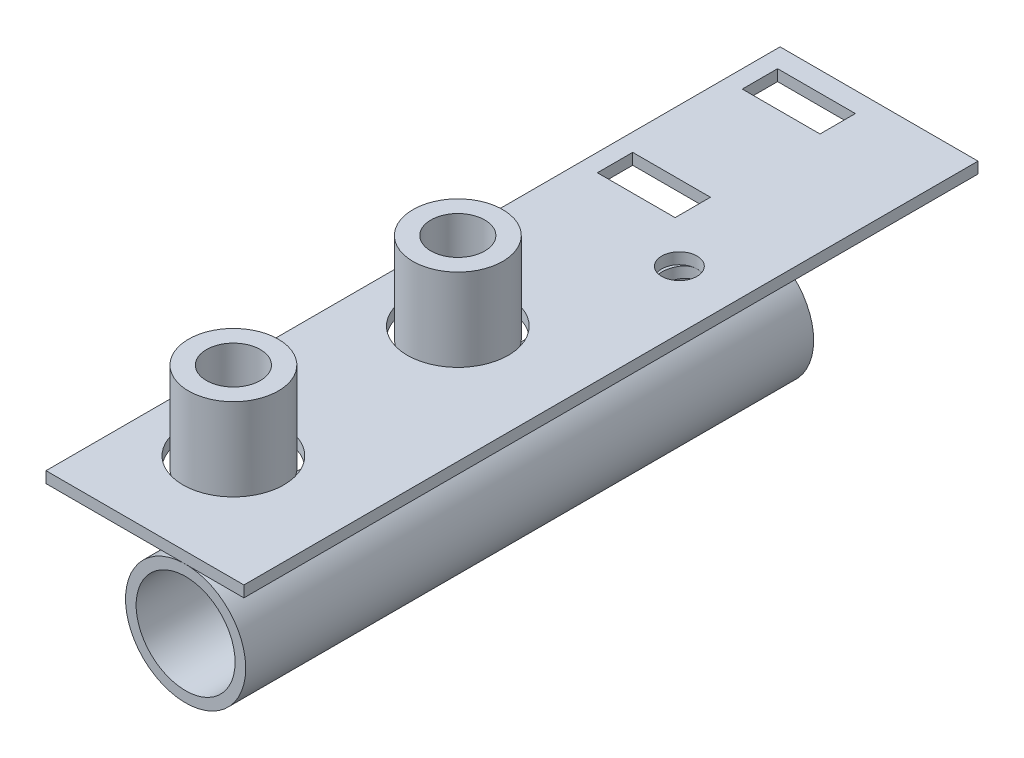
SolidWorks part; units mm, degrees
note: The reader was unsure of these and kept them because the rebuilt part matched: shared geometry of "Sketch6<4>".
other "DetailItem3"
other "Weld Folder"
ref_plane "Front Plane" through (0, 0, 0) normal (0, 0, 1) x (1, 0, 0)
ref_plane "Top Plane" through (0, 0, 0) normal (0, 1, 0) x (1, 0, 0)
ref_plane "Right Plane" through (0, 0, 0) normal (1, 0, 0) x (0, 0, -1)
sketch "Sketch1" plane through (0, 0, 0) normal (0, 1, 0) x (1, 0, 0)
  line L0 (-63.4061, 36.8) -> (49936.5939, 36.8) construction
  line L1 (16.5, -139.7) -> (-39.5, -139.7)
  line L2 (16.5, -139.7) -> (16.5, 68)
  line L3 (16.5, 68) -> (-39.5, 68)
  line L4 (-39.5, -139.7) -> (-39.5, 68)
  line L5 (16.5, -139.7) -> (-39.5, 68) construction
  line L6 (16.5, 68) -> (-39.5, -139.7) construction
  line L7 (-34.5, 62.3) -> (-12.5, 62.3)
  line L8 (-34.5, 62.3) -> (-34.5, 52.3)
  line L9 (-34.5, 52.3) -> (-12.5, 52.3)
  line L10 (-12.5, 62.3) -> (-12.5, 52.3)
  line L11 (-34.5, 62.3) -> (-12.5, 52.3) construction
  line L12 (-34.5, 52.3) -> (-12.5, 62.3) construction
  line L13 (-12.5, 11.3) -> (-12.5, 21.3)
  line L14 (-34.5, 11.3) -> (-12.5, 11.3)
  line L15 (-34.5, 11.3) -> (-34.5, 21.3)
  line L16 (-34.5, 21.3) -> (-12.5, 21.3)
  circle A0 centre (0, 0) radius 5
  point P4 (-11.5, -35.85)
  point P12 (-23.5, 57.3)
  dimension "D1" = 10
  dimension "D2" = 16.5
  dimension "D3" = 68
  dimension "D4" = 36.8
  dimension "D5" = 10.7
  dimension "D6" = 39.5
  dimension "D7" = 10
  dimension "D8" = 22
  dimension "D9" = 5
  dimension "D10" = 56
  dimension "D11" = 139.7
  dimension "D12" = 31
base flange "Base-Flange1" sketch "Sketch1" thickness 3.175 reverse thickness direction no parameters "D1"=10
sketch "Sketch7" plane through (0, 0, 0) normal (0, 0, 1) x (1, 0, 0)
  line L0 (-5, -3.175) -> (5, -3.175) construction
  line L1 (-5, -3.175) -> (5, -3.175) construction
  line L2 (0, -3.175) -> (0, -20.175) construction
  line L3 (16.5, -3.175) -> (16.5, 0) construction
  circle A0 centre (0, -20.175) radius 17
  circle A1 centre (0, -20.175) radius 14
  dimension "D1" = 34
  dimension "D2" = 28
  dimension "D3" = 16.5
extrude "Boss-Extrude2" add sketch "Sketch7" along normal up to surface (139.7 mm away) and the other way blind 21 separate body up to face at (-11.5, -1.5875, 139.7)
sketch "Sketch8" plane through (0, 0, 0) normal (0, 1, 0) x (1, 0, 0)
  circle A0 centre (0, 0) radius 5 construction
  circle A1 centre (0, 0) radius 5
extrude "Cut-Extrude1" cut sketch "Sketch8" against normal through all
sketch "Sketch6" plane through (0, 0, 0) normal (0, 1, 0) x (1, 0, 0)
  line L0 (-39.5, 68) -> (-39.5, -139.7) construction
  line L1 (-16.64, -109.5375) -> (-16.64, -46.0375) construction
  line L2 (1.0034, -77.7875) -> (-34.2834, -77.7875) construction
  line L3 (-39.5, -139.7) -> (16.5, -139.7) construction
  circle A0 centre (-16.64, -46.0375) radius 12.7
  circle A1 centre (-16.64, -46.0375) radius 7.62
  circle A2 centre (-16.64, -109.5375) radius 7.62
  circle A3 centre (-16.64, -109.5375) radius 12.7
  circle A4 centre (-16.64, -46.0375) radius 14.2875
  circle A5 centre (-16.64, -109.5375) radius 14.2875
  point P11 (-16.64, -77.7875)
  dimension "D3" = 5.08
  dimension "D4" = 1.5875
  dimension "1.2" = 25.4
  dimension "D1" = 22.86
  dimension "D2" = 46.0375
  dimension "D5" = 63.5
  dimension "D6" = 30.1625
  dimension "D7" = 93.6625
extrude "Cut-Extrude2" cut sketch "Sketch6" against normal up to next (3.175 mm away) contours A4 | A5
extrude "Boss-Extrude3" add sketch "Sketch6<4>" against normal up to surface (3.175 mm away) and the other way blind 22.225 separate body contours A2 | A3 | A1 | A0 up to face at (-11.5, -3.175, 35.85)
sketch "Sketch6<4>" plane through (0, 0, 0) normal (0, 1, 0) x (1, 0, 0) same geometry as "Sketch6"
sketch "Bend-Lines1" [suppressed] plane through (0, 0, 0) normal (0, 1, 0) x (1, 0, 0)
sketch "Bounding-Box1" [suppressed] plane through (0, 0, 0) normal (0, 1, 0) x (1, 0, 0)
sheet metal parameters "Sheet-Metal1" thickness 3.175 parameters "D1"=10
flat pattern "Flat-Pattern1" [suppressed]
sketch "Bend-Lines2" plane through (0, 0, 0) normal (0, 1, 0) x (1, 0, 0)
sketch3d "Bounding-Box2" [suppressed]
  line L0 (-39.5, 68, 0) -> (-39.5, -139.7, 0) construction
  line L1 (16.5, 68, 0) -> (16.5, -139.7, 0) construction
  line L2 (-39.5, 68, 0) -> (16.5, 68, 0) construction
  line L3 (-39.5, -139.7, 0) -> (16.5, -139.7, 0) construction
sheet metal parameters "Sheet-Metal5" thickness 3.175 parameters "D1"=10
flat pattern "Flat-Pattern1"
sketch "Bend-Lines2" plane through (0, 0, 0) normal (0, 1, 0) x (1, 0, 0)
sketch3d "Bounding-Box2" [suppressed]
  line L0 (-39.5, 68, 0) -> (-39.5, -139.7, 0) construction
  line L1 (16.5, 68, 0) -> (16.5, -139.7, 0) construction
  line L2 (-39.5, 68, 0) -> (16.5, 68, 0) construction
  line L3 (-39.5, -139.7, 0) -> (16.5, -139.7, 0) construction
